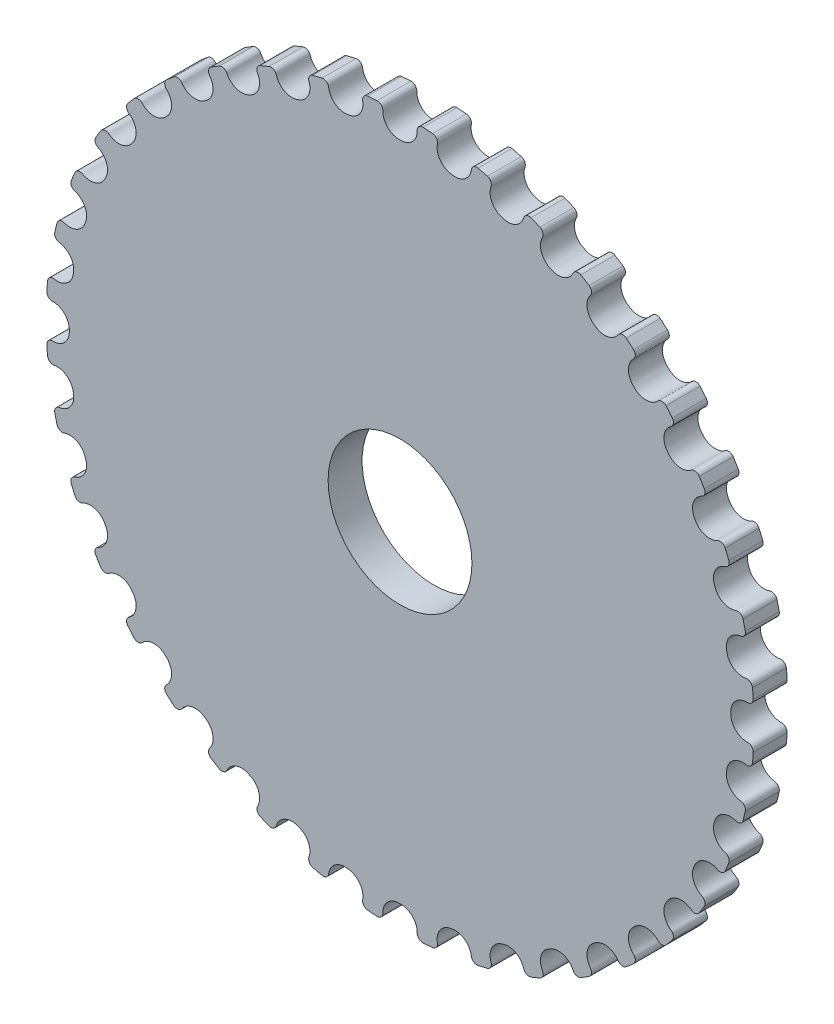
SolidWorks part; units mm, degrees
material "Thornel Mat VMA"
ref_plane "Front Plane" through (0, 0, 0) normal (0, 0, 1) x (1, 0, 0)
ref_plane "Top Plane" through (0, 0, 0) normal (0, 1, 0) x (1, 0, 0)
ref_plane "Right Plane" through (0, 0, 0) normal (1, 0, 0) x (0, 0, -1)
ref_axis "Axis1" through (0, 0, 55) along (0, 0, -1)
sketch "SketchRevolveGearBelt01" plane through (0, 0, 0) normal (1, 0, 0) x (0, 0, -1)
  line L0 (0, 0) -> (1, 0) construction
  line L1 (1.5, 0) -> (1.5, 31.2595)
  line L2 (1.5, 31.2595) -> (-1.5, 31.2595)
  line L3 (-1.5, 31.2595) -> (-1.5, 0)
  line L4 (-1.5, 0) -> (1.5, 0)
  dimension "GearBeltSide1" = 1.5
  dimension "GearBeltOutsideDiameter" = 31.2595
  dimension "GearBeltSide2" = 1.5
revolve "GearBelt01" add sketch "SketchRevolveGearBelt01" angle 360 about L0
sketch "SketchToothGearBelt01" plane through (0, 0, 0) normal (0, 0, 1) x (1, 0, 0)
  arc A0 (31.193, 2.0389) -> (31.193, -2.0389) centre (0, 0) cw
  spline S0 degree 3 poles (31.193, -2.0389) (31.1948, -2.0123) (31.1941, -1.9723) (31.1867, -1.9195) (31.178, -1.8806) (31.1661, -1.8425) (31.1511, -1.8054) (31.1331, -1.7698) (31.1123, -1.7357) (31.0888, -1.7034) (31.0627, -1.6731) (31.0343, -1.6451) (31.0036, -1.6195) (30.971, -1.5965) (30.9365, -1.5763) (30.9006, -1.5589) (30.8633, -1.5445) (30.825, -1.5332) (30.7859, -1.5251) (30.7463, -1.5201) (30.6992, -1.5186) (30.6277, -1.5196) (30.532, -1.516) (30.4198, -1.5026) (30.309, -1.4805) (30.2002, -1.4498) (30.0943, -1.4107) (29.9917, -1.3633) (29.8931, -1.3081) (29.7992, -1.2453) (29.7105, -1.1753) (29.6276, -1.0986) (29.5509, -1.0156) (29.481, -0.9268) (29.4182, -0.8329) (29.363, -0.7343) (29.3157, -0.6317) (29.2767, -0.5257) (29.246, -0.4169) (29.224, -0.3061) (29.2106, -0.1939) (29.2075, -0.1051) (29.2078, -0.0405) (29.2077, 0) (29.2078, 0.0405) (29.2075, 0.1051) (29.2106, 0.1939) (29.224, 0.3061) (29.246, 0.4169) (29.2767, 0.5257) (29.3157, 0.6317) (29.363, 0.7343) (29.4182, 0.8329) (29.481, 0.9268) (29.5509, 1.0156) (29.6276, 1.0986) (29.7105, 1.1753) (29.7992, 1.2453) (29.8931, 1.3081) (29.9917, 1.3633) (30.0943, 1.4107) (30.2002, 1.4498) (30.309, 1.4805) (30.4198, 1.5026) (30.532, 1.516) (30.6277, 1.5196) (30.6992, 1.5186) (30.7463, 1.5201) (30.7859, 1.5251) (30.825, 1.5332) (30.8633, 1.5445) (30.9006, 1.5589) (30.9365, 1.5763) (30.971, 1.5965) (31.0036, 1.6195) (31.0343, 1.6451) (31.0627, 1.6731) (31.0888, 1.7034) (31.1123, 1.7357) (31.1331, 1.7698) (31.1511, 1.8054) (31.1661, 1.8425) (31.178, 1.8806) (31.1867, 1.9195) (31.1941, 1.9723) (31.1948, 2.0123) (31.193, 2.0389) knots 0 0 0 0 0.012476 0.018713 0.024951 0.031189 0.037427 0.043665 0.049903 0.05614 0.062378 0.068616 0.074854 0.081092 0.08733 0.093567 0.099805 0.106043 0.112281 0.118519 0.124756 0.134376 0.152024 0.169672 0.18732 0.204968 0.222616 0.240264 0.257912 0.27556 0.293208 0.310856 0.328503 0.346151 0.363799 0.381447 0.399095 0.416743 0.434391 0.452039 0.469687 0.487335 0.493667 0.5 0.506333 0.512665 0.530313 0.547961 0.565609 0.583257 0.600905 0.618553 0.636201 0.653849 0.671497 0.689144 0.706792 0.72444 0.742088 0.759736 0.777384 0.795032 0.81268 0.830328 0.847976 0.865624 0.875244 0.881481 0.887719 0.893957 0.900195 0.906433 0.91267 0.918908 0.925146 0.931384 0.937622 0.94386 0.950097 0.956335 0.962573 0.968811 0.975049 0.981287 0.987524 1 1 1 1
extrude "ToothExtrudeCutGearBelt01" cut sketch "SketchToothGearBelt01" against normal blind 7.239 and the other way blind 7.239
pattern_circular "PatternGearBelt01" count 40 every 9 about axis through (0, 0, 55) along (0, 0, -1) of "ToothExtrudeCutGearBelt01"
sketch "BoreRevolveSketch" plane through (0, 0, 0) normal (1, 0, 0) x (0, 0, -1)
  line L0 (0, 0) -> (1, 0) construction
  line L1 (-7.239, 0) -> (7.239, 0)
  line L2 (7.239, 0) -> (7.239, 6.35)
  line L3 (7.239, 6.35) -> (-7.239, 6.35)
  line L4 (-7.239, 6.35) -> (-7.239, 0)
  dimension "BoreSide1" = 7.239
  dimension "TaperSide1" = 6.35
  dimension "BoreSide2" = 7.239
  dimension "TaperSide2" = 6.35
revolve "BoreRevolveCut" cut sketch "BoreRevolveSketch" angle 360 about L0
sketch "AuxiliarySketchGearBelt01" plane through (0, 0, 0) normal (0, 0, 1) x (1, 0, 0)
  circle A0 centre (0, 0) radius 31.831 construction
  dimension "PitchDiameter" = 63.6619
